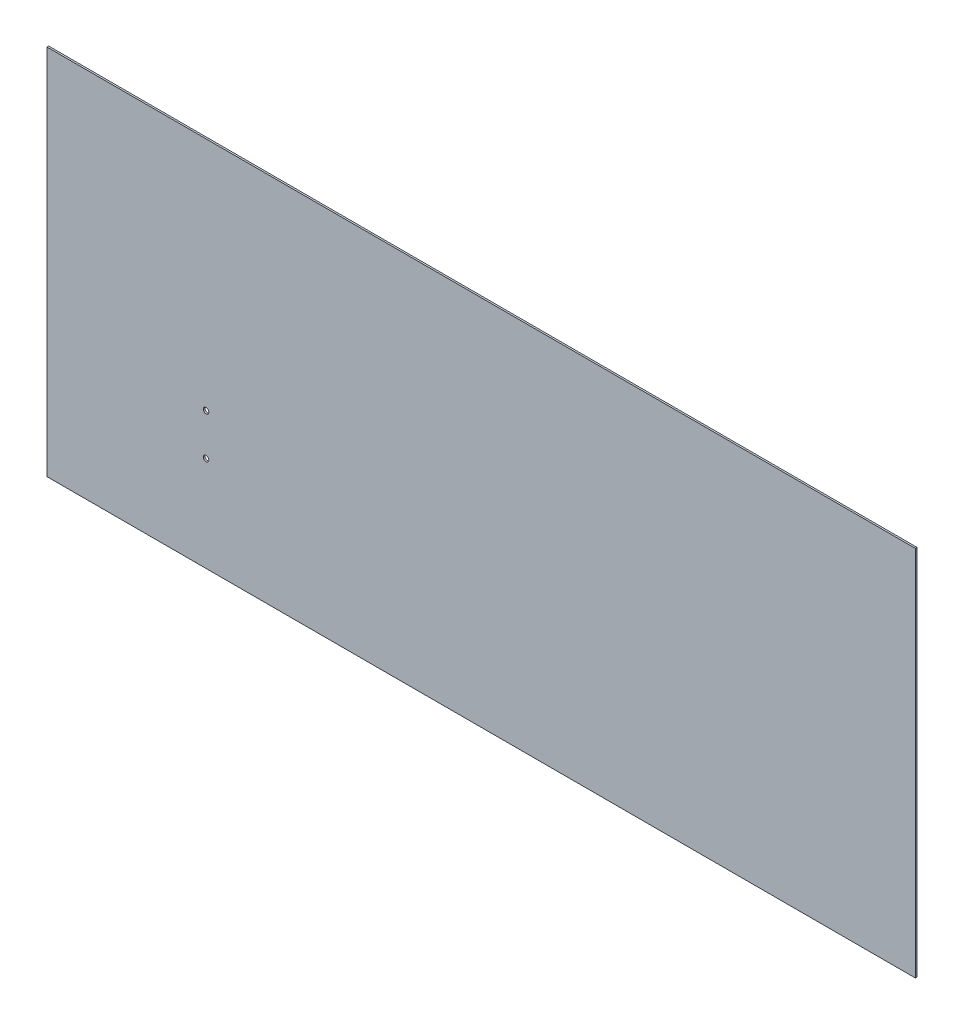
SolidWorks part; units mm, degrees
material "6061-T6 (SS)"
ref_plane "Front Plane" through (0, 0, 0) normal (0, 0, 1) x (1, 0, 0)
ref_plane "Top Plane" through (0, 0, 0) normal (0, 1, 0) x (1, 0, 0)
ref_plane "Right Plane" through (0, 0, 0) normal (1, 0, 0) x (0, 0, -1)
sketch "Sketch1" plane through (0, 0, 0) normal (0, 0, 1) x (1, 0, 0)
  line L1 (-400.177, -171.45) -> (400.177, -171.45)
  line L2 (-400.177, -171.45) -> (-400.177, 171.45)
  line L3 (-400.177, 171.45) -> (400.177, 171.45)
  line L4 (400.177, -171.45) -> (400.177, 171.45)
  line L5 (-400.177, -171.45) -> (400.177, 171.45) construction
  line L6 (-400.177, 171.45) -> (400.177, -171.45) construction
  point P0 (0, 0)
  dimension "D1" = 342.9
  dimension "D2" = 800.354
base flange "Base-Flange1" sketch "Sketch1" thickness 1.5875 reverse thickness direction no parameters "D1"=0.7366
hole_wizard "#10 Clearance Hole2" positions "Sketch5" profile "Sketch4" hole size "#10" standard "ANSI Inch" end condition through all
sketch "Sketch5" plane through (0, 0, -1.5875) normal (0, 0, -1) x (-1, 0, 0)
  point P0 (253.5301, -83.6265)
  point P3 (253.5301, -45.5265)
sketch "Sketch4" plane through (-253.5301, -83.6265, -1.5875) normal (1, 0, 0) x (0, 1, 0)
  line L0 (0, 0) -> (0, 1.5875)
  line L1 (0, 1.5875) -> (2.5527, 1.5875)
  line L2 (2.5527, 1.5875) -> (2.5527, 0)
  line L5 (2.5527, 0) -> (0, 0)
  line L11 (0, -6.35) -> (0, 107.95) construction
  dimension "Thru Hole Dia." = 5.1054
  dimension "Thru Hole Depth" = 1.5875
sketch "Bend-Lines1" [suppressed] plane through (0, 0, 0) normal (0, 1, 0) x (1, 0, 0)
sketch "Bounding-Box1" [suppressed] plane through (0, 0, 0) normal (0, 1, 0) x (1, 0, 0)
sheet metal parameters "Sheet-Metal1" thickness 1.5875 parameters "D1"=0.7366
flat pattern "Flat-Pattern1" [suppressed]
sketch "Bend-Lines2" plane through (0, 0, 0) normal (0, 1, 0) x (1, 0, 0)
sketch3d "Bounding-Box2" [suppressed]
  line L0 (-400.177, -171.45, 0) -> (400.177, -171.45, 0) construction
  line L1 (-400.177, 171.45, 0) -> (400.177, 171.45, 0) construction
  line L2 (-400.177, -171.45, 0) -> (-400.177, 171.45, 0) construction
  line L3 (400.177, -171.45, 0) -> (400.177, 171.45, 0) construction
sheet metal parameters "Sheet-Metal4" thickness 1.5875 parameters "D1"=0.7366
flat pattern "Flat-Pattern1"
sketch "Bend-Lines2" plane through (0, 0, 0) normal (0, 1, 0) x (1, 0, 0)
sketch3d "Bounding-Box2" [suppressed]
  line L0 (-400.177, -171.45, 0) -> (400.177, -171.45, 0) construction
  line L1 (-400.177, 171.45, 0) -> (400.177, 171.45, 0) construction
  line L2 (-400.177, -171.45, 0) -> (-400.177, 171.45, 0) construction
  line L3 (400.177, -171.45, 0) -> (400.177, 171.45, 0) construction
